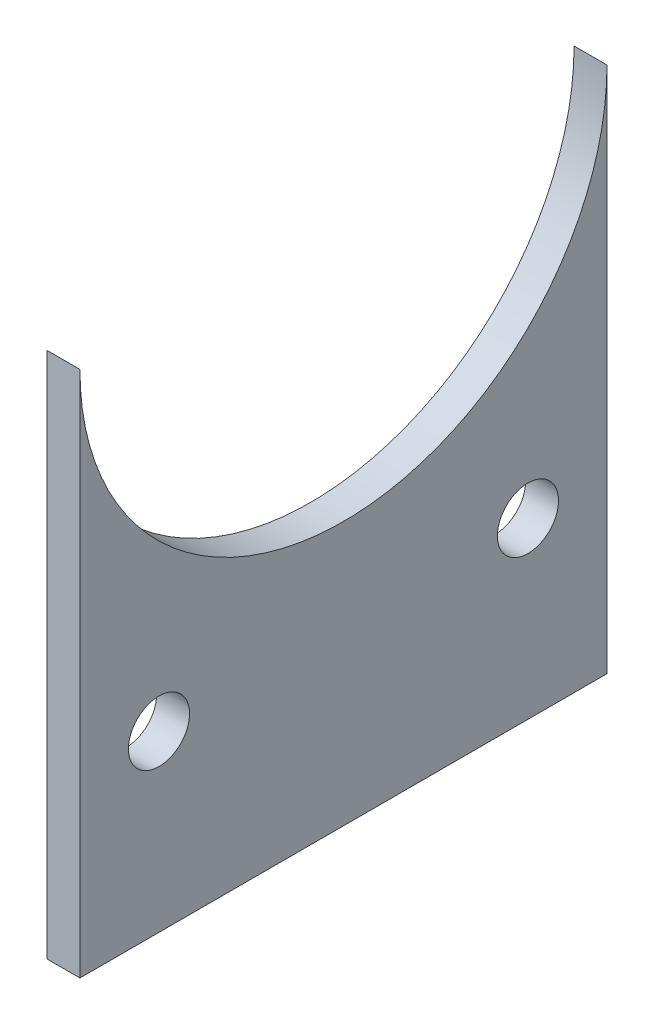
SolidWorks part; units mm, degrees
ref_plane "Front Plane" through (0, 0, 0) normal (0, 0, 1) x (1, 0, 0)
ref_plane "Top Plane" through (0, 0, 0) normal (0, 1, 0) x (1, 0, 0)
ref_plane "Right Plane" through (0, 0, 0) normal (1, 0, 0) x (0, 0, -1)
sketch "Sketch1" plane through (0, 0, 0) normal (1, 0, 0) x (0, 0, -1)
  line L1 (-12.7, -12.7) -> (12.7, -12.7)
  line L2 (-12.7, -12.7) -> (-12.7, 12.7)
  line L4 (12.7, -12.7) -> (12.7, 12.7)
  line L5 (-12.7, -12.7) -> (12.7, 12.7) construction
  line L6 (-12.7, 12.7) -> (12.7, -12.7) construction
  line L7 (-12.7, 12.7) -> (12.7, 12.7) construction
  arc A0 (-12.7, 12.7) -> (12.7, 12.7) centre (0, 12.7) ccw
  point P0 (0, 0)
  dimension "D1" = 25.4
  dimension "D3" = 25.4
extrude "Boss-Extrude1" add sketch "Sketch1" along normal blind 1.5875
sketch "Sketch6" plane through (0, 0, 0) normal (-1, 0, 0) x (0, 0, 1)
  circle A0 centre (-8.8899, -4.309) radius 1.4732
extrude "Cut-Extrude2" cut sketch "Sketch6" against normal through all both and the other way through all
mirror "Mirror2" about plane through (0, 0, 0) normal (0, 0, 1) of "Cut-Extrude2"
